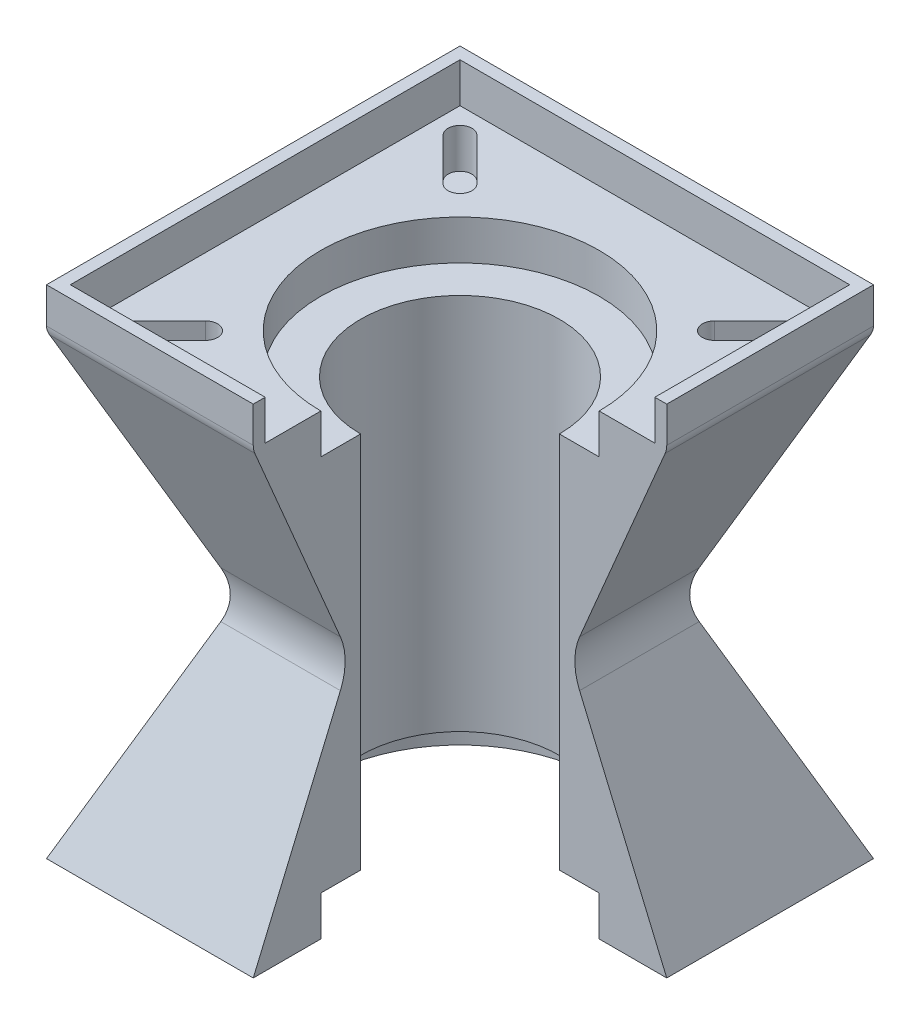
SolidWorks part; units mm, degrees
material "Cast Stainless Steel"
ref_plane "Front Plane" through (0, 0, 0) normal (0, 0, 1) x (1, 0, 0)
ref_plane "Top Plane" through (0, 0, 0) normal (0, 1, 0) x (1, 0, 0)
ref_plane "Right Plane" through (0, 0, 0) normal (1, 0, 0) x (0, 0, -1)
sketch "Sketch3" plane through (0, 0, 0) normal (0, 1, 0) x (1, 0, 0)
  line L1 (-52, 52) -> (52, 52)
  line L2 (-52, 52) -> (-52, -52)
  line L3 (-52, -52) -> (52, -52)
  line L4 (52, 52) -> (52, -52)
  line L5 (-52, 52) -> (52, -52) construction
  line L6 (-52, -52) -> (52, 52) construction
  point P0 (0, 0)
  dimension "D1" = 104
  dimension "D2" = 104
extrude "Boss-Extrude2" add sketch "Sketch3" along normal blind 57.5 draft 23
mirror "Mirror1" about plane through (0, 57.5, 0) normal (0, 1, 0) of bodies 102
sketch "Sketch4" plane through (0, 115, 0) normal (0, 1, 0) x (1, 0, 0)
  line L0 (-52, 52) -> (52, -52) construction
  line L1 (52, 52) -> (-52, -52) construction
  circle A0 centre (0, 0) radius 25
  dimension "D1" = 50
extrude "Cut-Extrude1" cut sketch "Sketch4" against normal through all
sketch "Sketch5" plane through (0, 115, 0) normal (0, 1, 0) x (1, 0, 0)
  line L0 (0, 0) -> (0, -52)
  line L1 (-52, -52) -> (52, -52) construction
  line L2 (0, 0) -> (52, 0)
  line L3 (52, -52) -> (52, 52) construction
  line L4 (0, -52) -> (52, -52)
  line L5 (52, -52) -> (52, 0)
  circle A0 centre (0, 0) radius 35
  circle M6 centre (0, 0) radius 25
  line M7 (52, -52) -> (52, 52)
  line M10 (-52, -52) -> (52, -52)
  dimension "D1" = 70
  dimension "D2" = 90
extrude "Cut-Extrude3" cut sketch "Sketch5" against normal through all contours A0 L0 L2 M10 M7 | L0 A0 L2 M6 | L2 L0 M6 region at (10.6103, 115, 10.6103) region at (19.2754, 115, 19.2754) region at (32.1561, 115, 32.1561)
sketch "Sketch7" plane through (0, 115, 0) normal (0, 1, 0) x (1, 0, 0)
  circle A0 centre (0, 0) radius 35
  dimension "D1" = 70
extrude "Cut-Extrude4" cut sketch "Sketch7" against normal blind 10
fillet "Fillet1" radius 15 4 edges at (-13.7963, 57.5, 27.5927) (-27.5927, 57.5, 0) (27.5927, 57.5, -13.7963) (0, 57.5, -27.5927)
sketch "Sketch9" plane through (0, 0, 0) normal (0, -1, 0) x (1, 0, 0)
  circle A0 centre (0, 0) radius 35
  dimension "D1" = 70
extrude "Cut-Extrude5" cut sketch "Sketch9" against normal blind 10
sketch "Sketch10" plane through (0, 115, 0) normal (0, 1, 0) x (1, 0, 0)
  line L0 (-52, 52) -> (52, 52)
  line L1 (52, 52) -> (52, 0)
  line L2 (-52, 52) -> (-52, -52)
  line L3 (-52, -52) -> (0, -52)
  line L4 (-49, -49) -> (0, -49)
  line L5 (-49, 49) -> (-49, -49)
  line L6 (-49, 49) -> (49, 49)
  line L7 (49, 49) -> (49, 0)
  line L8 (52, 0) -> (49, 0)
  line L9 (0, -49) -> (0, -52)
  dimension "D1" = 3
extrude "Boss-Extrude3" add sketch "Sketch10" along normal blind 10
sketch "Sketch11" plane through (0, 115, 0) normal (0, 1, 0) x (1, 0, 0)
  line L0 (0, 35) -> (0, -35) construction
  line L1 (-35, 0) -> (35, 0) construction
  line L2 (-42.5922, 42.5922) -> (-31.9856, 31.9856) construction
  line L3 (-40.4709, 44.7135) -> (-29.8643, 34.1069)
  line L4 (-44.7135, 40.4709) -> (-34.1069, 29.8643)
  line L5 (42.5922, 42.5922) -> (31.9856, 31.9856) construction
  line L6 (44.7135, 40.4709) -> (34.1069, 29.8643)
  line L7 (40.4709, 44.7135) -> (29.8643, 34.1069)
  line L11 (-42.5922, -42.5922) -> (-31.9856, -31.9856) construction
  line L12 (-44.7135, -40.4709) -> (-34.1069, -29.8643)
  line L13 (-40.4709, -44.7135) -> (-29.8643, -34.1069)
  line L14 (0, 0) -> (-42.5922, 42.5922) construction
  line L18 (42.5922, -42.5922) -> (31.9856, -31.9856) construction
  line L19 (40.4709, -44.7135) -> (29.8643, -34.1069)
  line L20 (44.7135, -40.4709) -> (34.1069, -29.8643)
  line L21 (42.5922, -42.5922) -> (31.9856, -31.9856) construction
  line L22 (40.4709, -44.7135) -> (29.8643, -34.1069)
  line L23 (44.7135, -40.4709) -> (34.1069, -29.8643)
  arc A0 (-40.4709, 44.7135) -> (-44.7135, 40.4709) centre (-42.5922, 42.5922) ccw
  arc A1 (-34.1069, 29.8643) -> (-29.8643, 34.1069) centre (-31.9856, 31.9856) ccw
  arc A2 (35, 0) -> (0, -35) centre (0, 0) ccw construction
  arc A3 (25, 0) -> (0, -25) centre (0, 0) ccw construction
  arc A4 (25, 0) -> (0, -25) centre (0, 0) ccw
  arc A5 (35, 0) -> (0, -35) centre (0, 0) ccw
  arc A6 (44.7135, 40.4709) -> (40.4709, 44.7135) centre (42.5922, 42.5922) ccw
  arc A7 (29.8643, 34.1069) -> (34.1069, 29.8643) centre (31.9856, 31.9856) ccw
  arc A10 (-44.7135, -40.4709) -> (-40.4709, -44.7135) centre (-42.5922, -42.5922) ccw
  arc A11 (-29.8643, -34.1069) -> (-34.1069, -29.8643) centre (-31.9856, -31.9856) ccw
  arc A16 (40.4709, -44.7135) -> (44.7135, -40.4709) centre (42.5922, -42.5922) ccw
  arc A17 (34.1069, -29.8643) -> (29.8643, -34.1069) centre (31.9856, -31.9856) ccw
  point P9 (-37.2889, 37.2889)
  point P14 (0, 0)
  point P20 (37.2889, 37.2889)
  point P24 (0, 0)
  point P35 (-37.2889, -37.2889)
  point P42 (37.2889, -37.2889)
  point P49 (37.2889, -37.2889)
  point P56 (37.2889, -37.2889)
  dimension "D2" = 3
  dimension "D3" = 135
  dimension "D5" = 31.9856
  dimension "D1" = 15
  dimension "D4" = 3
  dimension "D7" = 60.2345
  dimension "D6" = 4
extrude "Cut-Extrude6" cut sketch "Sketch11" against normal blind 10 contours L13 A11 L12 A10 | L4 A1 L3 A0 | L6 A7 L7 A6 region at (-37.2889, 115, 37.2889)
fillet "Fillet2" radius 5 4 edges at (-26, 115, 52) (52, 115, -26) (-52, 115, 0) (0, 115, -52)
equation "\"A\"= 115mm"
equation "\"B\"= 104mm"
equation "\"C\"= 23deg"
